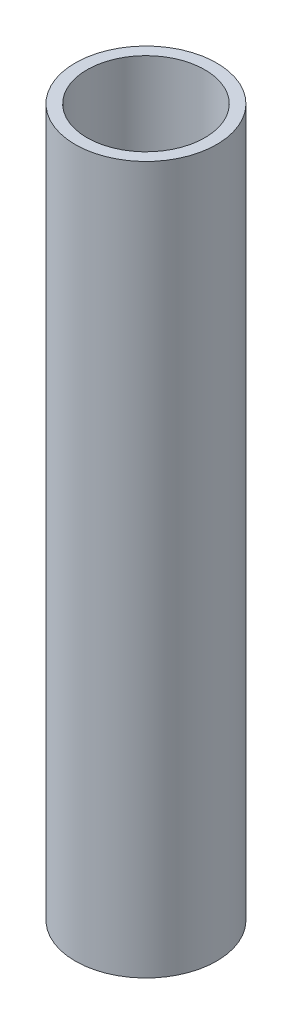
SolidWorks part; units mm, degrees
ref_plane "Front Plane" through (0, 0, 0) normal (0, 0, 1) x (1, 0, 0)
ref_plane "Top Plane" through (0, 0, 0) normal (0, 1, 0) x (1, 0, 0)
ref_plane "Right Plane" through (0, 0, 0) normal (1, 0, 0) x (0, 0, -1)
sketch "Sketch1" plane through (0, 0, 0) normal (0, 1, 0) x (1, 0, 0)
  circle A0 centre (0, 0) radius 30
  circle A1 centre (0, 0) radius 25
extrude "Boss-Extrude1" add sketch "Sketch1" along normal blind 300
